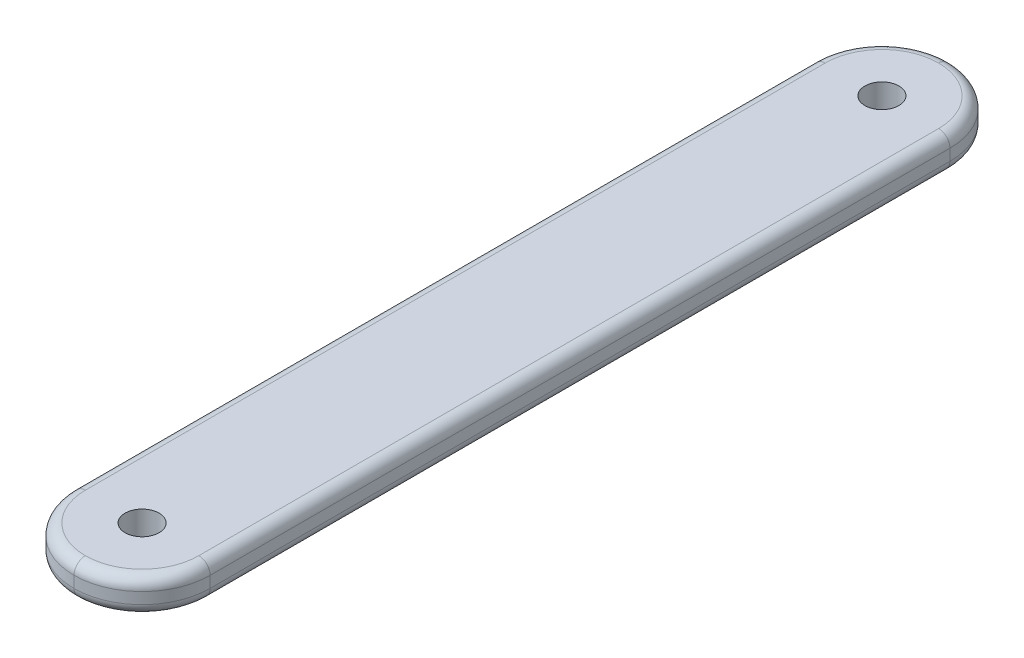
SolidWorks part; units mm, degrees
material "6061 Alloy"
ref_plane "Front Plane" through (0, 0, 0) normal (0, 0, 1) x (1, 0, 0)
ref_plane "Top Plane" through (0, 0, 0) normal (0, 1, 0) x (1, 0, 0)
ref_plane "Right Plane" through (0, 0, 0) normal (1, 0, 0) x (0, 0, -1)
sketch "Sketch1" plane through (0, 0, 0) normal (0, 1, 0) x (1, 0, 0)
  line L0 (0, 81.727) -> (0, -81.727) construction
  line L1 (-12.7, -81.727) -> (12.7, -81.727)
  line L2 (-12.7, -81.727) -> (-12.7, 81.727)
  line L3 (-12.7, 81.727) -> (12.7, 81.727)
  line L4 (12.7, -81.727) -> (12.7, 81.727)
  line L5 (-12.7, -81.727) -> (12.7, 81.727) construction
  line L6 (-12.7, 81.727) -> (12.7, -81.727) construction
  line L7 (0, 69.027) -> (-34.5135, -59.7792) construction
  line L8 (-34.5135, -59.7792) -> (0, -69.027) construction
  circle A0 centre (0, -69.027) radius 3.175
  circle A2 centre (0, 69.027) radius 3.175
  point P0 (0, 0)
  dimension "D3" = 15
  dimension "D1" = 6.35
  dimension "D2" = 25.4
  dimension "D4" = 133.35
  dimension "D5" = 138.0541
  dimension "D6" = 12.7
  dimension "D7" = 12.7
extrude "Boss-Extrude1" add sketch "Sketch1" along normal blind 6.35
fillet "Fillet2" radius 12.7 4 edges at (-12.7, 3.175, -81.727) (12.7, 3.175, -81.727) (-12.7, 3.175, 81.727) (12.7, 3.175, 81.727)
fillet "Fillet3" radius 2.1167 12 edges at (8.9803, 6.35, 78.0073) (-8.9803, 6.35, 78.0073) (-12.7, 6.35, 0) (-8.9803, 6.35, -78.0073) (8.9803, 6.35, -78.0073) (8.9803, 0, 78.0073) (-8.9803, 0, 78.0073) (-12.7, 0, 0) (-8.9803, 0, -78.0073) (8.9803, 0, -78.0073) (12.7, 6.35, 0) (12.7, 0, 0)
